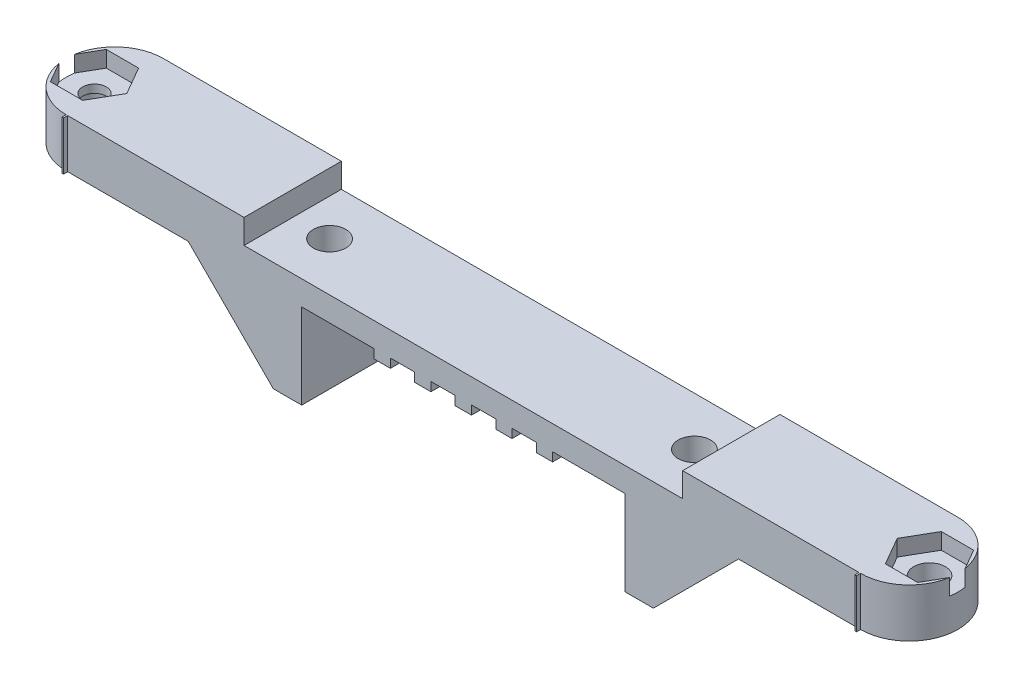
SolidWorks part; units mm, degrees
ref_plane "Front Plane" through (0, 0, 0) normal (0, 0, 1) x (1, 0, 0)
ref_plane "Top Plane" through (0, 0, 0) normal (0, 1, 0) x (1, 0, 0)
ref_plane "Right Plane" through (0, 0, 0) normal (1, 0, 0) x (0, 0, -1)
sketch "Sketch1" plane through (0, 0, 0) normal (0, 1, 0) x (1, 0, 0)
  line L0 (-49, 0) -> (49, 0) construction
  line L1 (-49, 6) -> (49, 6)
  line L2 (-49, -6) -> (49, -6)
  arc A0 (-49, 6) -> (-49, -6) centre (-49, 0) ccw
  arc A1 (49, -6) -> (49, 6) centre (49, 0) ccw
  circle A2 centre (-51.5, 0) radius 1.95
  circle A3 centre (51.5, 0) radius 1.95
  point P2 (0, 0)
  point P12 (-55, 0)
  point P13 (55, 0)
  dimension "D3" = 3.9
  dimension "D4" = 3.5
  dimension "D1" = 110
  dimension "D2" = 12
  dimension "D5" = 3.5
extrude "Boss-Extrude1" add sketch "Sketch1" along normal blind 3 contours L2 A1 L1 A0 | A2 | A3
sketch "Sketch4" plane through (0, 0, 0) normal (0, -1, 0) x (1, 0, 0)
  line L0 (-19.94, 6) -> (-19.94, -6)
  line L1 (-49, 6) -> (49, 6) construction
  line L2 (-49, -6) -> (49, -6) construction
  line L3 (-19.94, -6) -> (-23.44, -6)
  line L4 (-23.44, -6) -> (-23.44, 6)
  line L5 (-23.44, 6) -> (-19.94, 6)
  line L6 (0, 6) -> (0, -6) construction
  line L7 (-19.94, 5.075) -> (-19.94, -14.3256) construction
  line L8 (23.44, -6) -> (23.44, 6)
  line L9 (19.94, -6) -> (23.44, -6)
  line L10 (19.94, 6) -> (19.94, -6)
  line L11 (23.44, 6) -> (19.94, 6)
  dimension "D1" = 0
  dimension "D2" = 3.5
extrude "Boss-Extrude3" add sketch "Sketch4" along normal blind 10.5
sketch "Sketch5" plane through (0, 0, 0) normal (0, -1, 0) x (1, 0, 0)
  line L1 (4, 6) -> (4, -6)
  line L2 (4, 6) -> (6, 6)
  line L6 (-19.94, -6) -> (19.94, -6) construction
  line L7 (-1, 6) -> (1, 6)
  line L8 (-1, 6) -> (-1, -6)
  line L9 (-1, -6) -> (1, -6)
  line L10 (1, 6) -> (1, -6)
  line L11 (-1, 6) -> (1, -6) construction
  line L12 (-1, -6) -> (1, 6) construction
  line L13 (6, 6) -> (6, -6)
  line L14 (4, -6) -> (6, -6)
  line L15 (9, 6) -> (9, -6)
  line L16 (9, 6) -> (11, 6)
  line L17 (11, 6) -> (11, -6)
  line L18 (9, -6) -> (11, -6)
  line L19 (-4, 6) -> (-4, -6)
  line L20 (-6, -6) -> (-4, -6)
  line L21 (-6, 6) -> (-6, -6)
  line L22 (-6, 6) -> (-4, 6)
  line L23 (-9, 6) -> (-9, -6)
  line L24 (-11, -6) -> (-9, -6)
  line L25 (-11, 6) -> (-11, -6)
  line L26 (-11, 6) -> (-9, 6)
  point P0 (0, 0)
  dimension "D1" = 2
  dimension "D2" = 3
  dimension "D3" = 3
extrude "Boss-Extrude4" add sketch "Sketch5" along normal blind 1.1
sketch "Sketch6" plane through (0, 0, 6) normal (0, 0, 1) x (1, 0, 0)
  line L0 (49, 0) -> (49, 3)
  line L1 (49, 3) -> (48.8, 3)
  line L2 (-49, 3) -> (49, 3) construction
  line L3 (48.8, 3) -> (48.8, 0)
  line L4 (23.44, 0) -> (49, 0) construction
  line L5 (48.8, 0) -> (49, 0)
  line L6 (0, 0) -> (0, 3) construction
  line L7 (-48.8, 0) -> (-49, 0)
  line L8 (-48.8, 3) -> (-48.8, 0)
  line L9 (-49, 3) -> (-48.8, 3)
  line L10 (-49, 0) -> (-49, 3)
  dimension "D1" = 0.2
extrude "Boss-Extrude5" add sketch "Sketch6" along normal blind 0.5 contours L0 L1 L3 L5 | L8 L7 L10 L9
chamfer "Chamfer1" distance 10.5 2 edges at (23.44, 0, 0) (-23.44, 0, 0)
sketch "Sketch10" plane through (0, 3, 0) normal (0, 1, 0) x (1, 0, 0)
  line L0 (-27.05, -6) -> (-27.05, 6)
  line L1 (27.05, -6) -> (27.05, 6)
  line L4 (27.05, -6) -> (48.8, -6)
  line L5 (-27.05, 6) -> (-49, 6)
  line L6 (-27, -44.4532) -> (-27, 21.84) construction
  line L8 (-49, -6) -> (-49, -6.5)
  line L9 (-49, -6.5) -> (-48.8, -6.5)
  line L10 (-48.8, -6.5) -> (-48.8, -6)
  line L11 (-48.8, -6) -> (48.8, -6)
  line L12 (48.8, -6) -> (48.8, -6.5)
  line L13 (48.8, -6.5) -> (49, -6.5)
  line L14 (49, -6.5) -> (49, -6)
  line L15 (49, 6) -> (-49, 6)
  line L16 (-49, -6) -> (-49, -6.5)
  line L17 (-49, -6.5) -> (-48.8, -6.5)
  line L18 (-48.8, -6.5) -> (-48.8, -6)
  line L19 (-48.8, -6) -> (-27.05, -6)
  line L20 (48.8, -6) -> (48.8, -6.5)
  line L21 (48.8, -6.5) -> (49, -6.5)
  line L22 (49, -6.5) -> (49, -6)
  line L23 (49, 6) -> (27.05, 6)
  line L24 (27, 21.84) -> (27, -44.4532) construction
  circle A1 centre (51.5, 0) radius 1.45
  arc A2 (-49, 6) -> (-49, -6) centre (-49, 0) ccw
  arc A3 (49, -6) -> (49, 6) centre (49, 0) ccw
  arc A4 (-49, 6) -> (-49, -6) centre (-49, 0) ccw
  arc A5 (49, -6) -> (49, 6) centre (49, 0) ccw
  circle A7 centre (-51.5, 0) radius 1.45
  circle A8 centre (51.5, 0) radius 1.95 construction
  line M20 (-48.8, -6) -> (48.8, -6)
  line M21 (48.8, -6) -> (48.8, -6.5)
  line M22 (48.8, -6.5) -> (49, -6.5)
  line M23 (49, -6.5) -> (49, -6)
  arc M24 (49, -6) -> (49, 6) centre (49, 0) ccw
  line M25 (49, 6) -> (-49, 6)
  circle M26 centre (51.5, 0) radius 1.95
  dimension "D4" = 2.9
  dimension "D5" = 2.9
  dimension "D2" = 0.05
  dimension "D3" = 0.05
  dimension "D1" = 0
extrude "Boss-Extrude6" add sketch "Sketch10" along normal blind 3 contours L1 M20 M21 M22 M23 M24 M25 M26 | A4 L16 L17 L18 L19 L0 L5 | A7 region at (39.9878, 3, 0.002)
sketch "Sketch11" plane through (0, 6, 0) normal (0, 1, 0) x (1, 0, 0)
  line L1 (-53.4919, 3.45) -> (-55.4837, 0)
  line L2 (-55.4837, 0) -> (-53.4919, -3.45)
  line L3 (-53.4919, -3.45) -> (-49.5081, -3.45)
  line L4 (-49.5081, -3.45) -> (-47.5163, 0)
  line L5 (-47.5163, 0) -> (-49.5081, 3.45)
  line L6 (-49.5081, 3.45) -> (-53.4919, 3.45)
  line L8 (-48.8, -6) -> (-27.05, -6) construction
  line L9 (0, 0) -> (0, -50000) construction
  line L10 (49.5081, 3.45) -> (53.4919, 3.45)
  line L11 (47.5163, 0) -> (49.5081, 3.45)
  line L12 (49.5081, -3.45) -> (47.5163, 0)
  line L13 (53.4919, -3.45) -> (49.5081, -3.45)
  line L14 (55.4837, 0) -> (53.4919, -3.45)
  line L15 (53.4919, 3.45) -> (55.4837, 0)
  circle A0 centre (-51.5, 0) radius 3.45 construction
  circle M15 centre (-51.5, 0) radius 1.45
  dimension "D1" = 6.9
extrude "Cut-Extrude1" cut sketch "Sketch11" against normal blind 2 contours L15 L10 L11 L12 L13 L14 | L5 L6 L1 L2 L3 L4 M15 region at (-51.5, 6, -3.3446) region at (51.5, 6, 0)
sketch "Sketch12" plane through (0, 3, 0) normal (0, 1, 0) x (1, 0, 0)
  circle A0 centre (-22.5, 0) radius 2 construction
  circle A1 centre (22.5, 0) radius 2 construction
  circle A2 centre (-22.5, 0) radius 2
  circle A3 centre (22.5, 0) radius 2
sketch "Sketch13" plane through (0, 3, 0) normal (0, 1, 0) x (1, 0, 0)
  circle A0 centre (22.5, 0) radius 2 construction
  circle A1 centre (-22.5, 0) radius 2 construction
  circle A2 centre (22.5, 0) radius 2
  circle A3 centre (-22.5, 0) radius 2
extrude "Cut-Extrude2" cut sketch "Sketch13" against normal blind 8
